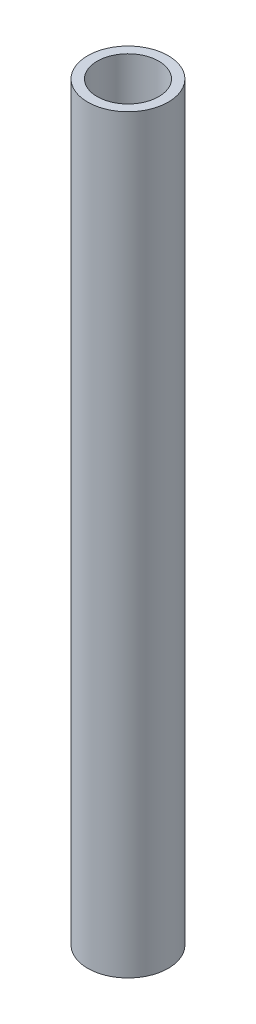
SolidWorks part; units mm, degrees
ref_plane "Front Plane" through (0, 0, 0) normal (0, 0, 1) x (1, 0, 0)
ref_plane "Top Plane" through (0, 0, 0) normal (0, 1, 0) x (1, 0, 0)
ref_plane "Right Plane" through (0, 0, 0) normal (1, 0, 0) x (0, 0, -1)
ref_axis "Axial" through (0, 55, 0) along (0, -1, 0)
ref_plane "Bottom Plane" through (0, -12.065, 0) normal (0, 1, 0) x (1, 0, 0)
sketch "Sketch1" plane through (0, 0, 0) normal (0, 1, 0) x (1, 0, 0)
  circle A0 centre (0, 0) radius 0.4953
  circle A1 centre (0, 0) radius 0.6477
  dimension "D1" = 0.9906
  dimension "D2" = 1.2954
extrude "Needle" add sketch "Sketch1" against normal blind 12.065
